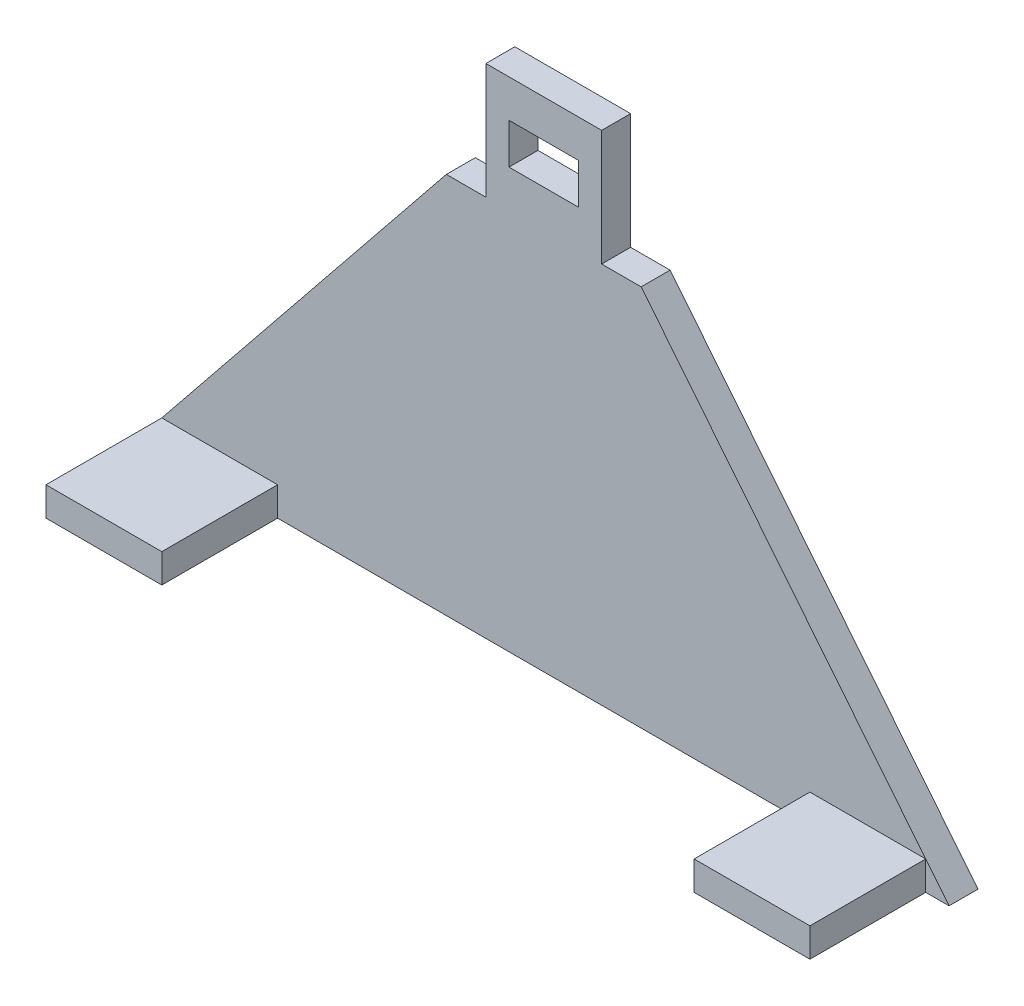
SolidWorks part; units mm, degrees
ref_plane "Front Plane" through (0, 0, 0) normal (0, 0, 1) x (1, 0, 0)
ref_plane "Top Plane" through (0, 0, 0) normal (0, 1, 0) x (1, 0, 0)
ref_plane "Right Plane" through (0, 0, 0) normal (1, 0, 0) x (0, 0, -1)
sketch "Sketch1" plane through (0, 0, 0) normal (0, 0, 1) x (1, 0, 0)
  line L0 (-35, 0) -> (35, 0)
  line L1 (35, 0) -> (8.412, 33)
  line L2 (8.412, 33) -> (5, 33)
  line L3 (5, 33) -> (5, 43)
  line L4 (5, 43) -> (-5, 43)
  line L5 (-5, 43) -> (-5, 33)
  line L6 (-5, 33) -> (-8.412, 33)
  line L7 (-8.412, 33) -> (-35, 0)
  point P4 (0, 0)
  point P9 (0, 43)
  point P11 (-8.412, 33)
  dimension "D1" = 70
  dimension "D2" = 43
  dimension "D3" = 10
  dimension "D4" = 10
  dimension "D5" = 10
base flange "Base-Flange1" sketch "Sketch1" thickness 2.5 reverse thickness direction no parameters "D1"=1
sketch "Sketch6" plane through (0, 0, 0) normal (0, 0, 1) x (1, 0, 0)
  line L0 (5, 43) -> (-5, 43) construction
  line L1 (-3, 39.75) -> (3, 39.75)
  line L2 (-3, 39.75) -> (-3, 36.25)
  line L3 (-3, 36.25) -> (3, 36.25)
  line L4 (3, 39.75) -> (3, 36.25)
  line L5 (5, 33) -> (5, 43) construction
  line L6 (-5, 43) -> (-5, 33) construction
  point P4 (0, 39.75)
  point P7 (0, 43)
  point P8 (3, 38)
  point P11 (5, 38)
  point P12 (-3, 38)
  point P15 (-5, 38)
  dimension "D1" = 6
  dimension "D2" = 3.5
extrude "Cut-Extrude1" cut sketch "Sketch6" against normal blind 10
sketch "Sketch7" plane through (0, 0, 0) normal (0, 0, 1) x (1, 0, 0)
  line L0 (-8.412, 33) -> (-35, 0) construction
  line L1 (-32.9858, 2.5) -> (-22.9858, 2.5)
  line L2 (-32.9858, 2.5) -> (-32.9858, 0)
  line L3 (-32.9858, 0) -> (-22.9858, 0)
  line L4 (-22.9858, 2.5) -> (-22.9858, 0)
  line L5 (-35, 0) -> (35, 0) construction
  dimension "D1" = 2.5
  dimension "D2" = 10
extrude "Boss-Extrude1" add sketch "Sketch7" along normal blind 10
mirror "Mirror1" about plane through (0, 0, 0) normal (1, 0, 0) of "Boss-Extrude1"
sketch "Bend-Lines1" [suppressed] plane through (0, 0, 0) normal (0, 1, 0) x (1, 0, 0)
sketch "Bounding-Box1" [suppressed] plane through (0, 0, 0) normal (0, 1, 0) x (1, 0, 0)
sheet metal parameters "Sheet-Metal1" thickness 2.5 parameters "D1"=1
flat pattern "Flat-Pattern1" [suppressed]
sketch "Bend-Lines2" plane through (0, 0, 0) normal (0, 1, 0) x (1, 0, 0)
sketch3d "Bounding-Box2" [suppressed]
  line L0 (35, 0, 0) -> (-35, 0, 0) construction
  line L1 (35, 43, 0) -> (-35, 43, 0) construction
  line L2 (35, 0, 0) -> (35, 43, 0) construction
  line L3 (-35, 0, 0) -> (-35, 43, 0) construction
sheet metal parameters "Sheet-Metal2" thickness 2.5 parameters "D1"=1
flat pattern "Flat-Pattern1"
sketch "Bend-Lines2" plane through (0, 0, 0) normal (0, 1, 0) x (1, 0, 0)
sketch3d "Bounding-Box2" [suppressed]
  line L0 (-35, 0, 0) -> (35, 0, 0) construction
  line L1 (-35, 43, 0) -> (35, 43, 0) construction
  line L2 (-35, 0, 0) -> (-35, 43, 0) construction
  line L3 (35, 0, 0) -> (35, 43, 0) construction
sheet metal parameters "Sheet-Metal3" thickness 2.5 parameters "D1"=1
flat pattern "Flat-Pattern1"
sketch "Bend-Lines2" plane through (0, 0, 0) normal (0, 1, 0) x (1, 0, 0)
sketch3d "Bounding-Box2" [suppressed]
  line L0 (-35, 0, 0) -> (35, 0, 0) construction
  line L1 (-35, 43, 0) -> (35, 43, 0) construction
  line L2 (-35, 0, 0) -> (-35, 43, 0) construction
  line L3 (35, 0, 0) -> (35, 43, 0) construction
sheet metal parameters "Sheet-Metal4" thickness 2.5 parameters "D1"=1
flat pattern "Flat-Pattern1"
sketch "Bend-Lines2" plane through (0, 0, 0) normal (0, 1, 0) x (1, 0, 0)
sketch3d "Bounding-Box2" [suppressed]
  line L0 (-35, 0, 0) -> (35, 0, 0) construction
  line L1 (-35, 43, 0) -> (35, 43, 0) construction
  line L2 (-35, 0, 0) -> (-35, 43, 0) construction
  line L3 (35, 0, 0) -> (35, 43, 0) construction
